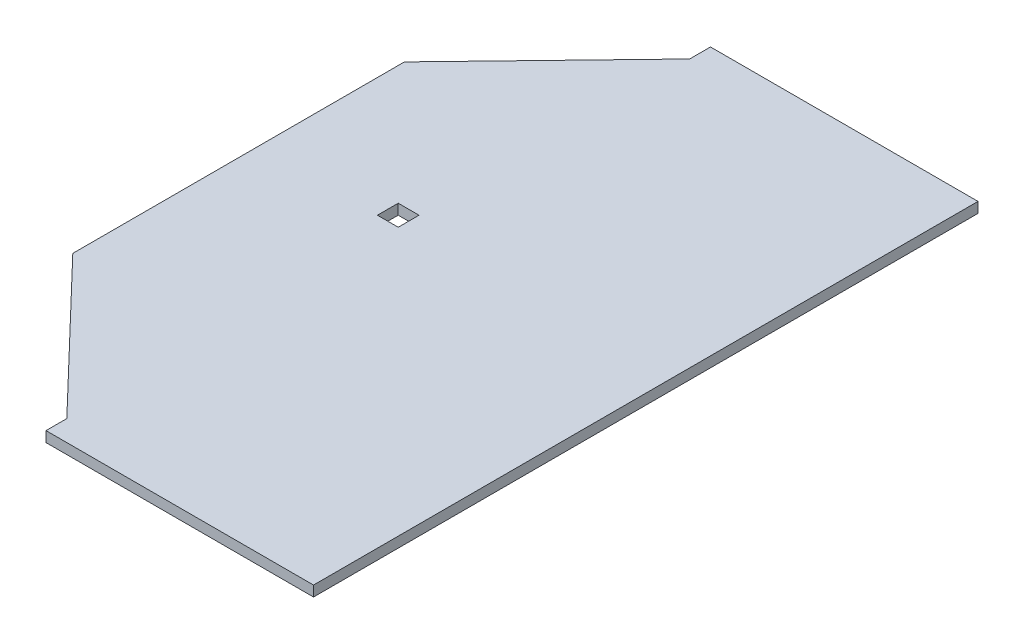
SolidWorks part; units mm, degrees
ref_plane "Front Plane" through (0, 0, 0) normal (0, 0, 1) x (1, 0, 0)
ref_plane "Top Plane" through (0, 0, 0) normal (0, 1, 0) x (1, 0, 0)
ref_plane "Right Plane" through (0, 0, 0) normal (1, 0, 0) x (0, 0, -1)
sketch "Sketch1" plane through (0, 0, 0) normal (0, 1, 0) x (1, 0, 0)
  line L1 (0, 0) -> (257, 0)
  line L3 (0, 638.38) -> (257, 638.38)
  line L4 (257, 0) -> (257, 638.38)
  line L14 (-134.58, 319.6109) -> (-134.58, 478.9059)
  line L18 (-134.58, 319.6109) -> (-134.58, 160.3159)
  line L20 (0, 638.38) -> (0, 618.38)
  line L21 (0, 618.38) -> (-134.58, 478.9059)
  line L22 (0, 0) -> (0, 20)
  line L23 (0, 20) -> (-134.58, 160.3159)
  point P5 (0, 0)
  dimension "D1" = 257
  dimension "D2" = 638.38
  dimension "D3" = 159.295
  dimension "D4" = 159.295
  dimension "D5" = 20
  dimension "D6" = 20
extrude "Boss-Extrude2" add sketch "Sketch1" along normal blind 10
sketch "Sketch4" plane through (0, 10, 0) normal (0, 1, 0) x (1, 0, 0)
  line L2 (0, 358.38) -> (-20, 358.38)
  line L3 (0, 358.38) -> (0, 338.38)
  line L4 (0, 338.38) -> (-20, 338.38)
  line L5 (-20, 358.38) -> (-20, 338.38)
  dimension "D2" = 20
  dimension "D3" = 20
extrude "Cut-Extrude1" cut sketch "Sketch4" against normal blind 10
